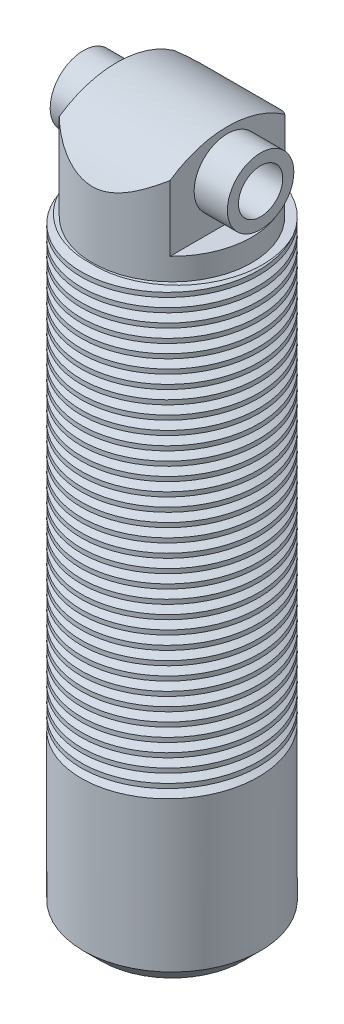
SolidWorks part; units mm, degrees
ref_plane "Front Plane" through (0, 0, 0) normal (0, 0, 1) x (1, 0, 0)
ref_plane "Top Plane" through (0, 0, 0) normal (0, 1, 0) x (1, 0, 0)
ref_plane "Right Plane" through (0, 0, 0) normal (1, 0, 0) x (0, 0, -1)
sketch "Sketch1" plane through (0, 0, 0) normal (0, 1, 0) x (1, 0, 0)
  circle A0 centre (0, 0) radius 18
  dimension "D1" = 36
extrude "Boss-Extrude1" add sketch "Sketch1" along normal blind 175
fillet "Fillet1" radius 6 1 edges at (0, 175, 18)
sketch "Sketch2" plane through (0, 0, 0) normal (0, 0, 1) x (1, 0, 0)
  line L0 (0, 175) -> (0, 88.5362) construction
  line L1 (12, 175) -> (-12, 175) construction
  line L2 (-30.561, 162.5) -> (-30.561, 142.5)
  line L3 (-12.5, 142.5) -> (-30.561, 142.5)
  line L4 (12.5, 162.5) -> (30.561, 162.5)
  line L5 (12.5, 162.5) -> (12.5, 142.5)
  line L6 (12.5, 142.5) -> (30.561, 142.5)
  line L7 (30.561, 162.5) -> (30.561, 142.5)
  line L8 (-12.5, 162.5) -> (-12.5, 142.5)
  line L9 (-12.5, 162.5) -> (-30.561, 162.5)
  dimension "D1" = 20
  dimension "D2" = 25
  dimension "D3" = 12.5
extrude "Cut-Extrude1" cut sketch "Sketch2" against normal through all both and the other way through all
sketch "Sketch5" plane through (0, 0, 0) normal (0, -1, 0) x (1, 0, 0)
  circle A0 centre (0, 0) radius 20
  dimension "D1" = 40
extrude "Boss-Extrude3" add sketch "Sketch5" against normal blind 137.5
sketch "Sketch6" plane through (0, 137.5, 0) normal (0, 1, 0) x (1, 0, 0)
  circle A0 centre (0, 0) radius 20 construction
  circle A1 centre (0, 0) radius 20
curve "Helix/Spiral1" pitch 3 height 100 radius 20 centre (0, 137.5, 0) axis (0, -1, 0) start towards (0, 0, 1)
sketch "Sketch7" plane through (0, 0, 0) normal (1, 0, 0) x (0, 0, -1)
  line L0 (-20, 138.5) -> (-20, 136.5)
  line L1 (-20, 136.5) -> (-18.2679, 137.5)
  line L2 (-18.2679, 137.5) -> (-20, 138.5)
  line L3 (-20, 137.5) -> (-18.2679, 137.5) construction
  dimension "D1" = 2
  dimension "D2" = 2
  dimension "D3" = 2
sweep "Cut-Sweep1" cut profiles "Sketch7" path "Helix/Spiral1" align with end faces yes
sketch "Sketch8" plane through (0, 0, 0) normal (0, -1, 0) x (1, 0, 0)
  circle A0 centre (0, 0) radius 10
  dimension "D1" = 20
extrude "Cut-Extrude3" cut sketch "Sketch8" against normal up to surface (137.5 mm away) up to face at (0, 137.5, -18)
chamfer "Chamfer1" distance 4 angle 45 1 edges at (0, 0, -20)
sketch "Sketch9" plane through (0, 0, 0) normal (1, 0, 0) x (0, 0, -1)
  circle A0 centre (0, 152.5) radius 7.5
  circle A1 centre (0, 152.5) radius 5
  dimension "D1" = 15
  dimension "D2" = 10
extrude "Boss-Extrude4" add sketch "Sketch9" along normal mid plane 40
extrude "Cut-Extrude4" cut sketch "Sketch9<2>" against normal through all both and the other way through all contours A1 region at (0, 152.5, 0)
sketch "Sketch9<2>" plane through (0, 0, 0) normal (1, 0, 0) x (0, 0, -1) same geometry as "Sketch9"
sketch "Sketch10" plane through (0, 0, 0) normal (1, 0, 0) x (0, 0, -1)
  line L1 (-32.0984, 184.5607) -> (42.127, 184.5607)
  line L2 (-32.0984, 184.5607) -> (-32.0984, 165.3416)
  line L3 (-32.0984, 165.3416) -> (42.127, 165.3416)
  line L4 (42.127, 184.5607) -> (42.127, 165.3416)
extrude "Cut-Extrude5" cut sketch "Sketch10" against normal through all both and the other way through all
fillet "Fillet2" radius 2.5 1 edges at (0, 165.3416, -18)
sketch "Sketch11" plane through (0, 0, 0) normal (1, 0, 0) x (0, 0, -1)
  line L0 (-18, 162.8416) -> (-18, 137.5) construction
  line L1 (18, 137.5) -> (18, 162.8416) construction
  line L2 (-18, 152.3987) -> (-18, 177.7603)
  line L3 (-18, 177.7603) -> (18, 177.7603)
  line L4 (18, 177.7603) -> (18, 152.3987)
  arc A0 (-18, 152.3987) -> (18, 152.3987) centre (0, 138.8987) cw
  dimension "D1" = 22.5
extrude "Cut-Extrude6" cut sketch "Sketch11" against normal through all both and the other way through all
